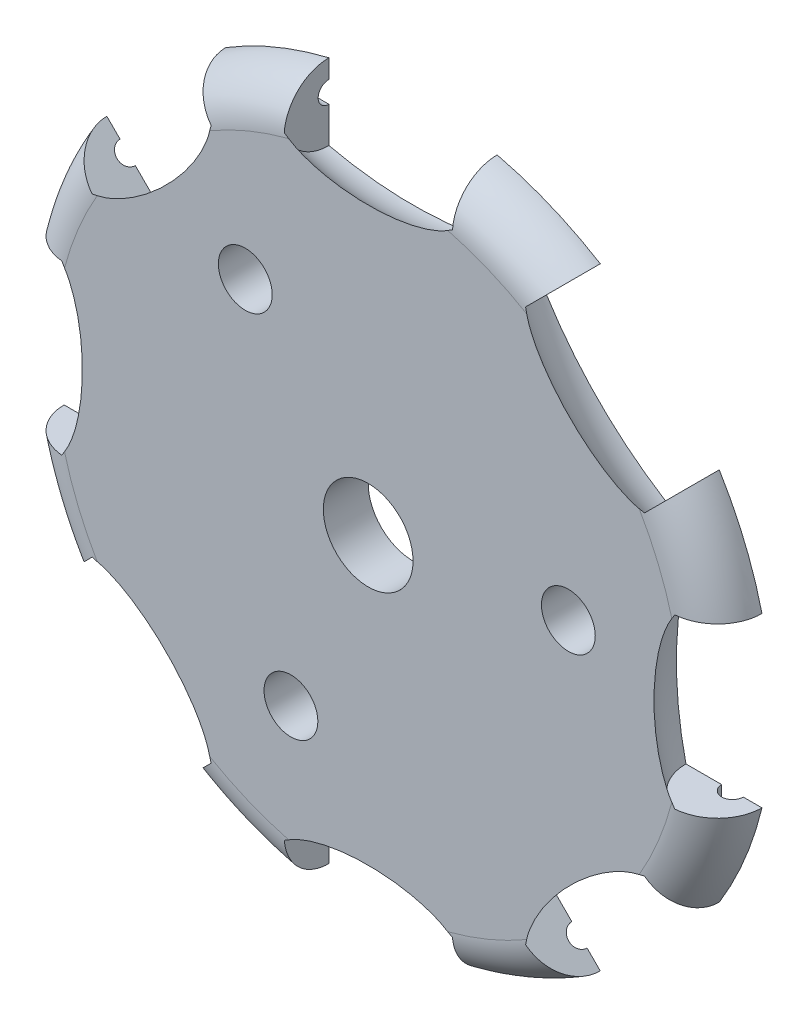
SolidWorks part; units mm, degrees
ref_plane "Front Plane" through (0, 0, 0) normal (0, 0, 1) x (1, 0, 0)
ref_plane "Top Plane" through (0, 0, 0) normal (0, 1, 0) x (1, 0, 0)
ref_plane "Right Plane" through (0, 0, 0) normal (1, 0, 0) x (0, 0, -1)
sketch "Sketch1" plane through (0, 0, 0) normal (0, 0, 1) x (1, 0, 0)
  circle A0 centre (0, 0) radius 25.4
  dimension "D1" = 50.8
extrude "Boss-Extrude1" add sketch "Sketch1" along normal blind 3.175
fillet "Fillet1" radius 3.1852 1 edges at (25.4, 0, 3.175)
sketch "Sketch2" plane through (0, 0, 3.175) normal (0, 0, 1) x (1, 0, 0)
  line L0 (0, 0) -> (-9.7202, -23.4665) construction
  line L1 (0, 0) -> (0, -6.9354) construction
  circle A0 centre (-5.4676, -13.1999) radius 1.905
  circle A1 centre (-8.6977, 11.335) radius 1.905
  circle A2 centre (14.1653, 1.8649) radius 1.905
  circle A3 centre (0, 0) radius 3.175
  circle A4 centre (0, 0) radius 25.4 construction
  point P4 (-5.4676, -13.1999)
  point P9 (0, 0)
  dimension "D2" = 3.81
  dimension "D4" = 6.35
  dimension "D1" = 14.2875
  dimension "D5" = 22.5
  dimension "D3" = 3
extrude "Cut-Extrude1" cut sketch "Sketch2" against normal through all
sketch "Sketch5" plane through (0, 0, 0) normal (0, 0, 1) x (1, 0, 0)
  line L0 (-5.9531, 22.606) -> (5.9531, 22.606)
  line L1 (5.9531, 22.606) -> (5.9531, 25.8994)
  line L2 (-5.9531, 22.606) -> (-5.9531, 25.8994)
  line L3 (-5.9531, 22.606) -> (-8.5086, 22.606) construction
  arc A0 (-5.9531, 25.8994) -> (5.9531, 25.8994) centre (0, 0) cw
  circle A1 centre (0, 0) radius 25.4 construction
  point P5 (0, 22.606)
  point P9 (0, 26.5748)
  dimension "D1" = 11.9062
  dimension "D2" = 22.606
  dimension "D3" = 7.9375
revolve "Cut-Revolve1" cut sketch "Sketch5" angle 360 about L3
sketch "Sketch6" plane through (0, 0, 0) normal (1, 0, 0) x (0, 0, -1)
  line L0 (0, -25.4) -> (0, 24.6925) construction
  circle A0 centre (0, 22.606) radius 0.762
  arc A1 (-3.163, 21.6886) -> (0, 19.3126) centre (0, 22.606) ccw construction
  dimension "D1" = 1.524
extrude "Cut-Extrude2" cut sketch "Sketch6" against normal mid plane 15.24
pattern_circular "CirPattern1" count 8 over 360 about axis through (0, 0, 0) along (0, 0, 1) of "Cut-Revolve1", "Cut-Extrude2"
